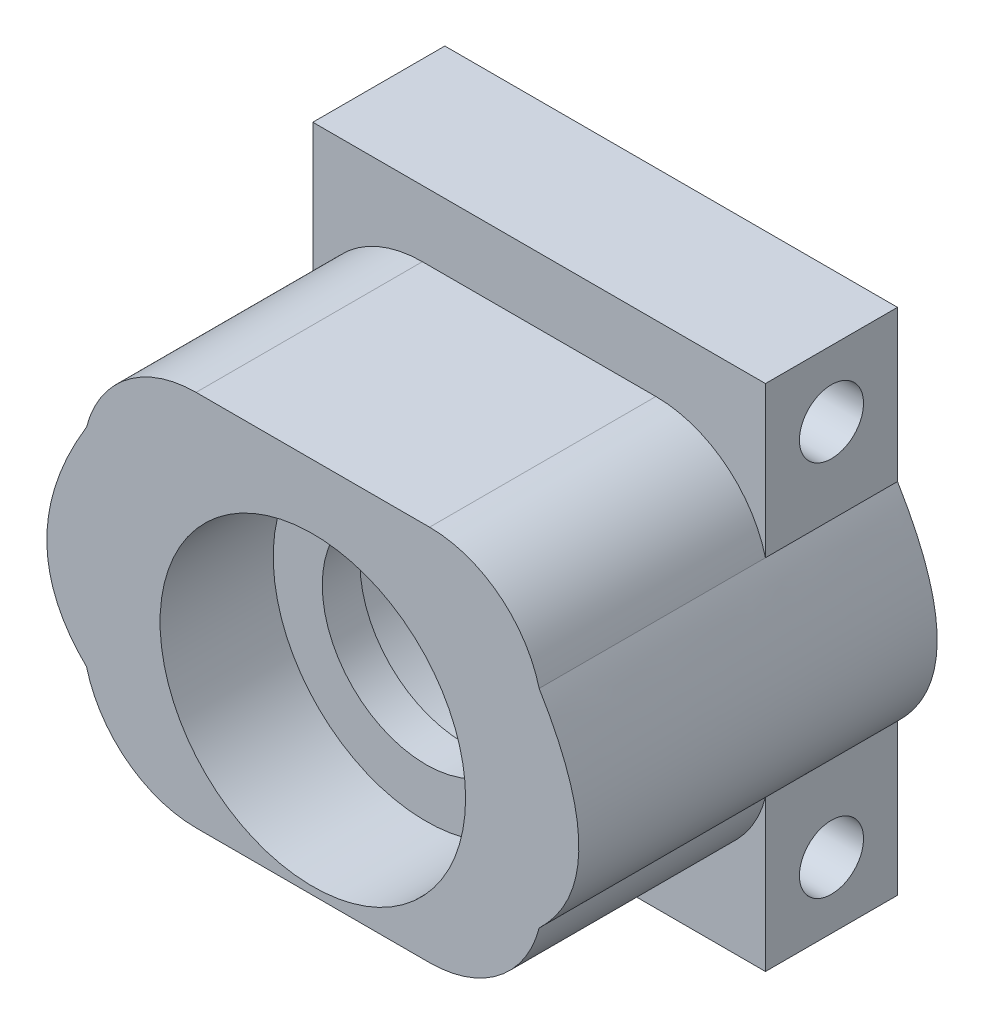
SolidWorks part; units mm, degrees
material "PLA"
ref_plane "Front Plane" through (0, 0, 0) normal (0, 0, 1) x (1, 0, 0)
ref_plane "Top Plane" through (0, 0, 0) normal (0, 1, 0) x (1, 0, 0)
ref_plane "Right Plane" through (0, 0, 0) normal (1, 0, 0) x (0, 0, -1)
sketch "Sketch1" plane through (0, 0, 0) normal (0, 0, 1) x (1, 0, 0)
  line L0 (-12, 13.5) -> (-12, 10)
  line L1 (-12, 10) -> (12, 10)
  line L2 (12, 10) -> (12, 13.5)
  line L3 (12, 13.5) -> (-12, 13.5)
  line L4 (-12, -10) -> (-12, -13.5)
  line L5 (-12, -13.5) -> (12, -13.5)
  line L6 (12, -13.5) -> (12, -10)
  line L7 (12, -10) -> (-12, -10)
  line L8 (0, 10.0333) -> (0, -15.702) construction
  line L9 (-12, 10) -> (-12, -10) construction
  line L10 (12, 10) -> (12, -10) construction
  line L11 (12, 10) -> (12, 5.5)
  line L12 (12, -10) -> (12, -5.5)
  line L13 (10, 10) -> (10, 5.5)
  line L14 (10, -10) -> (10, -5.5)
  line L17 (-10, -10) -> (-10, -5.5)
  line L18 (0, 0) -> (14.9553, 0) construction
  line L19 (-12, -10) -> (-12, -5.5)
  line L20 (-12, 10) -> (-12, 5.5)
  line L21 (-10, 10) -> (-10, 5.5)
  circle A0 centre (0, -1.5) radius 8.1
  circle A1 centre (0, -1.5) radius 5.5
  spline S0 degree 2 poles (12, 5.5) (16.2082, -1.4527) (12, -5.5) knots 0 0 0 0.703674 0.703674 0.703674
  spline S1 degree 2 poles (5.9341, -10) (5.4786, -10.0093) (0, -10) knots 0.968743 0.968743 0.968743 1 1 1
  spline S2 degree 2 poles (10, 5.5) (13.145, -1.5935) (10, -5.5) knots 0 0 0 0.703674 0.703674 0.703674
  spline S3 degree 2 poles (-12, 5.5) (-16.2082, -1.4527) (-12, -5.5) knots 0 0 0 0.703674 0.703674 0.703674
  spline S4 degree 2 poles (-10, 5.5) (-13.145, -1.5935) (-10, -5.5) knots 0 0 0 0.703674 0.703674 0.703674
  point P9 (0, -10)
  point P21 (12, 7.75)
  dimension "D6" = 8
  dimension "D8" = 16.2
  dimension "D9" = 11
  dimension "D10" = 1.5
  dimension "D5" = 8
  dimension "D1" = 3.5
  dimension "D2" = 3.5
  dimension "D3" = 24
  dimension "D4" = 27
  dimension "D7" = 2
extrude "Boss-Extrude1" add sketch "Sketch1" along normal blind 7 contours L2 L3 L0 L1 | S4 L21 L1 L20 S3 L19 L7 L17 | L13 S2 L14 L7 L12 S0 L11 L1 | L7 S1 L4 L5 L6 | L21 S4 L17 L7 L14 S2 L13 L1 A0 region at (0, 11.75, 0) region at (-11.7448, -0.0184, 0) region at (0, 9.6941, 0) region at (11.7448, -0.0184, 0) region at (-0.0008, -11.7504, 0)
extrude "Boss-Extrude2" add sketch "Sketch1<3>" along normal blind 12 from surface contours L21 S4 L17 L7 L14 S2 L13 L1 A0 | S4 L21 L1 L20 S3 L19 L7 L17 | L13 S2 L14 L7 L12 S0 L11 L1 region at (-11.7448, -0.0184, 0) region at (0, 9.6941, 0) region at (11.7448, -0.0184, 0) starting at face at (4.4506, -10, 7)
sketch "Sketch1<3>" plane through (0, 0, 0) normal (0, 0, 1) x (1, 0, 0) same geometry as "Sketch1"
sketch "Sketch2" plane through (-12, 0, 0) normal (-1, 0, 0) x (0, 0, 1)
  line L0 (7, -13.5) -> (0, -13.5) construction
  line L3 (3.5, 10) -> (3.5, -10) construction
  line L4 (7, -10) -> (7, -13.5) construction
  line L5 (0, -13.5) -> (0, -5.5) construction
  point P0 (3.5, 10)
  point P1 (3.5, -10)
  dimension "D1" = 20
  dimension "D2" = 3.5
hole_wizard "M3 Clearance Hole1" positions "Sketch3" profile "Sketch4" hole size "M3" standard "ISO" end condition through all
sketch "Sketch3" plane through (-12, 0, 0) normal (-1, 0, 0) x (0, 0, 1)
  point P0 (3.5, 10)
  point P3 (3.5, -10)
sketch "Sketch4" plane through (-12, 10, 3.5) normal (0, 1, 0) x (0, 0, 1)
  line L0 (0, 0) -> (0, 26.1041)
  line L1 (0, 26.1041) -> (1.7, 26.1041)
  line L2 (1.7, 26.1041) -> (1.7, 0)
  line L5 (1.7, 0) -> (0, 0)
  line L11 (0, -6.35) -> (0, 107.95) construction
  dimension "Thru Hole Dia." = 3.4
  dimension "Thru Hole Depth" = 26.1041
sketch "Sketch5" plane through (0, 13.5, 0) normal (0, 1, 0) x (1, 0, 0)
  line L0 (12, 0) -> (-12, 0) construction
  point P0 (0, -14)
  dimension "D1" = 14
fillet "Fillet1" radius 6 4 edges at (-12, 10, 13) (12, 10, 13) (12, -10, 13) (-12, -10, 13)
extrude "Boss-Extrude3" add sketch "Sketch1<4>" along normal blind 2 from offset 11 contours A0 A1 region at (-7.8709, -1.5, 0)
sketch "Sketch1<4>" plane through (0, 0, 0) normal (0, 0, 1) x (1, 0, 0) same geometry as "Sketch1"
fillet "Fillet2" radius 2 1 edges at (8.1, -1.5, 0)
